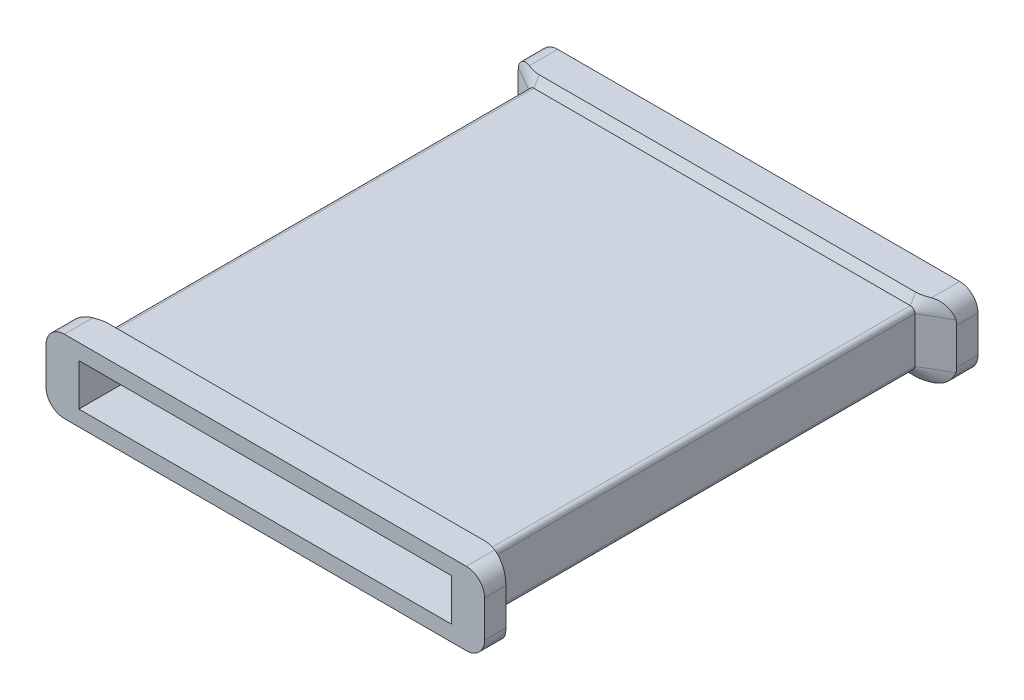
SolidWorks part; units mm, degrees
material "ABS"
ref_plane "Front Plane" through (0, 0, 0) normal (0, 0, 1) x (1, 0, 0)
ref_plane "Top Plane" through (0, 0, 0) normal (0, 1, 0) x (1, 0, 0)
ref_plane "Right Plane" through (0, 0, 0) normal (1, 0, 0) x (0, 0, -1)
sketch "Sketch1" plane through (0, 0, 0) normal (0, 0, 1) x (1, 0, 0)
  line L0 (0, 8) -> (48, 8)
  line L3 (48, 8) -> (48, 0)
  line L4 (48, 0) -> (0, 0)
  line L5 (0, 0) -> (0, 8)
  line L9 (3.6, 6.3) -> (44.4, 6.3)
  line L10 (3.6, 6.3) -> (3.6, 1.7)
  line L11 (3.6, 1.7) -> (44.4, 1.7)
  line L12 (44.4, 6.3) -> (44.4, 1.7)
  dimension "D1" = 1.7
  dimension "D2" = 40.8
  dimension "D4" = 4.6
  dimension "D5" = 1.7
  dimension "D7" = 3.6
  dimension "D8" = 3.6
extrude "Boss-Extrude1" add sketch "Sketch1" along normal blind 54
sketch "Sketch2" plane through (0, 0, 54) normal (0, 0, 1) x (1, 0, 0)
  line L1 (3.4, 7) -> (44.6, 7)
  line L2 (2.9, 6.5) -> (2.9, 1.5)
  line L3 (3.4, 1) -> (44.6, 1)
  line L4 (45.1, 6.5) -> (45.1, 1.5)
  line L5 (3.6, 1.7) -> (44.4, 1.7) construction
  line L6 (44.4, 6.3) -> (3.6, 6.3) construction
  line L8 (3.6, 6.3) -> (3.6, 1.7) construction
  line L9 (44.4, 1.7) -> (44.4, 6.3) construction
  arc A0 (2.9, 1.5) -> (3.4, 1) centre (3.4, 1.5) ccw
  arc A1 (44.6, 1) -> (45.1, 1.5) centre (44.6, 1.5) ccw
  arc A2 (44.6, 7) -> (45.1, 6.5) centre (44.6, 6.5) cw
  arc A3 (3.4, 7) -> (2.9, 6.5) centre (3.4, 6.5) ccw
  dimension "D1" = 0.5
  dimension "D2" = 0.7
  dimension "D3" = 0.7
  dimension "D4" = 0.7
  dimension "D5" = 0.7
extrude "Cut-Extrude1" cut sketch "Sketch2" against normal offset from surface (50 mm away) 2 from offset 2 flip side to cut up to face at (24, 4, 0) offset against normal yes
fillet "Fillet1" radius 2 8 edges at (48, 8, 53) (48, 0, 53) (48, 0, 1) (48, 8, 1) (0, 0, 1) (0, 8, 1) (0, 0, 53) (0, 8, 53)
chamfer "Chamfer4" distance 2 angle 60 16 edges at (2.9, 4, 52) (3.0464, 1.1464, 52) (3.0464, 6.8536, 52) (24, 1, 52) (24, 7, 52) (44.9536, 1.1464, 52) (44.9536, 6.8536, 52) (45.1, 4, 52) (2.9, 4, 2) (3.0464, 1.1464, 2) (3.0464, 6.8536, 2) (24, 1, 2) (24, 7, 2) (44.9536, 1.1464, 2) (44.9536, 6.8536, 2) (45.1, 4, 2) first distance on face at (2.9, 4, 27) first distance on face at (3.0982, 1.1982, 27) first distance on face at (3.0982, 6.8018, 27) first distance on face at (24, 1, 27) first distance on face at (24, 7, 27) first distance on face at (44.9018, 1.1982, 27) first distance on face at (44.9018, 6.8018, 27) first distance on face at (45.1, 4, 27)
